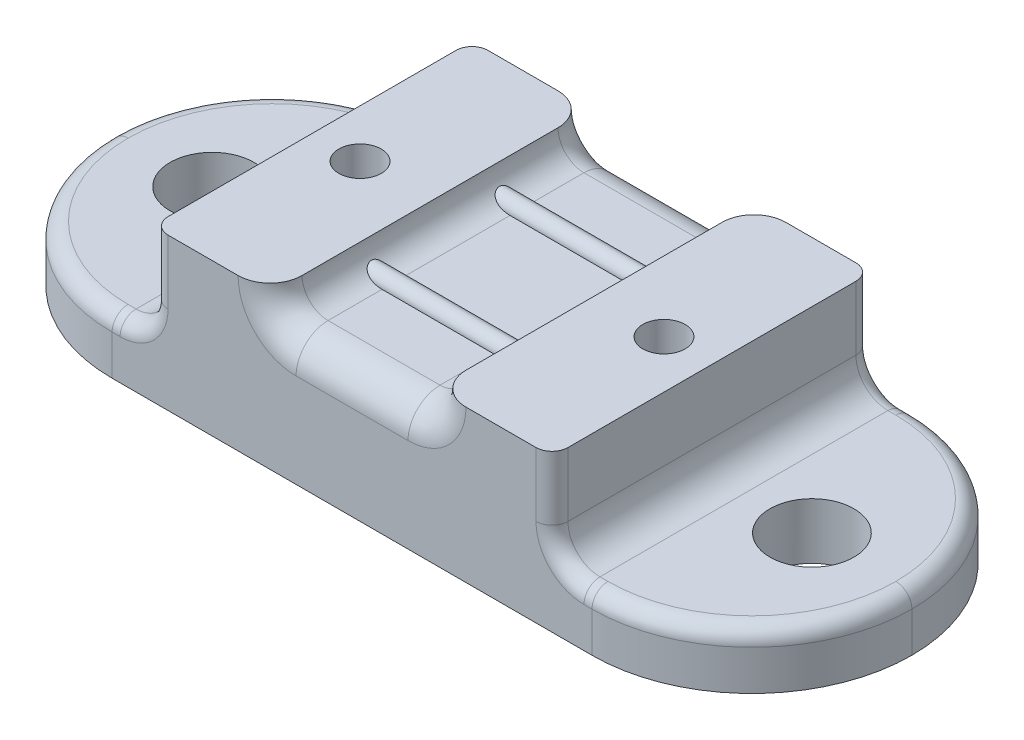
SolidWorks part; units mm, degrees
ref_plane "Front Plane" through (0, 0, 0) normal (0, 0, 1) x (1, 0, 0)
ref_plane "Top Plane" through (0, 0, 0) normal (0, 1, 0) x (1, 0, 0)
ref_plane "Right Plane" through (0, 0, 0) normal (1, 0, 0) x (0, 0, -1)
sketch "Sketch1" plane through (0, 0, 0) normal (0, 1, 0) x (1, 0, 0)
  line L1 (0, 0) -> (50, 0)
  line L2 (0, 0) -> (0, 20)
  line L3 (0, 20) -> (50, 20)
  line L4 (50, 0) -> (50, 20)
  dimension "D1" = 20
  dimension "D2" = 50
extrude "Boss-Extrude1" add sketch "Sketch1" along normal blind 3.5
sketch "Sketch2" plane through (0, 3.5, 0) normal (0, 1, 0) x (1, 0, 0)
  line L0 (50, 20) -> (0, 20) construction
  line L1 (12.5, 20) -> (37.5, 20)
  line L2 (12.5, 20) -> (12.5, 0)
  line L3 (12.5, 0) -> (37.5, 0)
  line L4 (37.5, 20) -> (37.5, 0)
  line L5 (0, 0) -> (50, 0) construction
  point P8 (25, 0)
  point P9 (25, 0)
  dimension "D1" = 25
extrude "Boss-Extrude2" add sketch "Sketch2" along normal blind 6
sketch "Sketch3" plane through (0, 3.5, 0) normal (0, 1, 0) x (1, 0, 0)
  line L0 (50, 0) -> (50, 20) construction
  line L1 (50, 20) -> (37.5, 20) construction
  line L2 (12.5, 20) -> (0, 20) construction
  circle A0 centre (6.25, 10) radius 2.625
  circle A1 centre (43.75, 10) radius 2.625
  point P6 (50, 10)
  point P9 (43.75, 20)
  point P13 (6.25, 20)
  dimension "D1" = 5.25
extrude "Cut-Extrude1" cut sketch "Sketch3" against normal blind 6
sketch "Sketch4" plane through (0, 0, 0) normal (0, 0, 1) x (1, 0, 0)
  line L1 (21.5, 9.5) -> (28.5, 9.5) construction
  line L2 (21.5, 11.125) -> (28.5, 11.125)
  line L3 (21.5, 7.875) -> (28.5, 7.875)
  line L4 (12.5, 9.5) -> (37.5, 9.5) construction
  arc A1 (21.5, 11.125) -> (21.5, 7.875) centre (21.5, 9.5) ccw
  arc A2 (28.5, 7.875) -> (28.5, 11.125) centre (28.5, 9.5) ccw
  point P2 (25, 9.5)
  point P9 (25, 9.5)
  dimension "D1" = 7
  dimension "D2" = 3.25
extrude "Cut-Extrude2" cut sketch "Sketch4" against normal blind 50
sketch "Sketch5" plane through (0, 9.5, 0) normal (0, 1, 0) x (1, 0, 0)
  line L0 (50, 0) -> (50, 20) construction
  line L1 (15.5, 10) -> (34.5, 10) construction
  line L2 (21.5, 20) -> (28.5, 20) construction
  line L3 (12.5, 20) -> (12.5, 0) construction
  circle A0 centre (15.5, 10) radius 1.325
  circle A1 centre (34.5, 10) radius 1.325
  point P4 (25, 10)
  point P7 (50, 10)
  point P10 (25, 20)
  dimension "D2" = 2.65
  dimension "D1" = 3
extrude "Cut-Extrude3" cut sketch "Sketch5" against normal blind 7
fillet "Fillet1" radius 10 4 edges at (0, 1.75, -20) (0, 1.75, 0) (50, 1.75, -20) (50, 1.75, 0)
fillet "Fillet2" radius 2 2 edges at (37.5, 3.5, -10) (12.5, 3.5, -10)
sketch "Sketch6" plane through (37.5, 0, 0) normal (1, 0, 0) x (0, 0, -1)
  line L0 (6, 7.875) -> (14, 7.875) construction
  line L1 (0, 9.5) -> (20, 9.5) construction
  line L2 (20, 7.875) -> (0, 7.875) construction
  circle A0 centre (6, 7.875) radius 0.625
  circle A1 centre (14, 7.875) radius 0.625
  point P6 (10, 9.5)
  point P7 (10, 7.875)
  dimension "D1" = 1.25
  dimension "D2" = 8
extrude "Boss-Extrude3" add sketch "Sketch6" against normal up to surface (25 mm away) up to face at (12.5, 7.5, -10)
fillet "Fillet3" radius 2 6 edges at (20.351, 8.351, -20) (29.649, 8.351, -20) (20.351, 8.351, 0) (29.649, 8.351, 0) (25, 7.875, -20) (25, 7.875, 0)
fillet "Fillet4" radius 1 16 edges at (37.5, 7.5, 0) (38.0858, 4.0858, 0) (39.75, 3.5, 0) (37.5, 7.5, -20) (38.0858, 4.0858, -20) (39.75, 3.5, -20) (47.0711, 3.5, -17.0711) (12.5, 7.5, -20) (11.9142, 4.0858, -20) (10.25, 3.5, -20) (2.9289, 3.5, -17.0711) (12.5, 7.5, 0) (11.9142, 4.0858, 0) (10.25, 3.5, 0) (47.0711, 3.5, -2.9289) (2.9289, 3.5, -2.9289)
